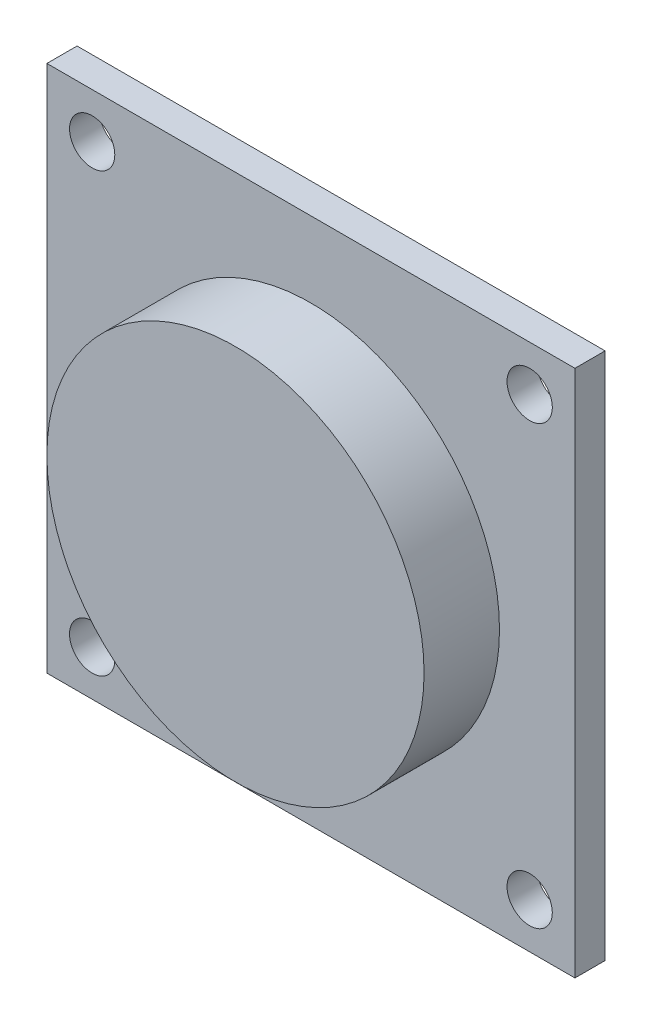
SolidWorks part; units mm, degrees
ref_plane "Front Plane" through (0, 0, 0) normal (0, 0, 1) x (1, 0, 0)
ref_plane "Top Plane" through (0, 0, 0) normal (0, 1, 0) x (1, 0, 0)
ref_plane "Right Plane" through (0, 0, 0) normal (1, 0, 0) x (0, 0, -1)
sketch "Sketch1" plane through (0, 0, 0) normal (0, 0, 1) x (1, 0, 0)
  line L1 (35, 35) -> (-35, 35)
  line L2 (35, 35) -> (35, -35)
  line L3 (35, -35) -> (-35, -35)
  line L4 (-35, 35) -> (-35, -35)
  line L5 (35, 35) -> (-35, -35) construction
  line L6 (35, -35) -> (-35, 35) construction
  point P0 (0, 0)
  dimension "D1" = 70
  dimension "D2" = 70
extrude "Boss-Extrude1" add sketch "Sketch1" along normal blind 4
sketch "Sketch2" plane through (0, 0, 4) normal (0, 0, 1) x (1, 0, 0)
  circle A0 centre (0, 0) radius 25
  dimension "D1" = 50
extrude "Boss-Extrude2" add sketch "Sketch2" along normal blind 10
sketch "Sketch3" plane through (0, 0, 0) normal (0, 0, -1) x (-1, 0, 0)
  circle A0 centre (0, 0) radius 25
  dimension "D1" = 50
extrude "Cut-Extrude1" cut sketch "Sketch3" against normal blind 4
fillet "Fillet1" radius 4 1 edges at (-25, 0, 0)
sketch "Sketch4" plane through (0, 0, 4) normal (0, 0, 1) x (1, 0, 0)
  line L0 (-39.3388, 0) -> (37.8701, 0) construction
  line L1 (0, 42.9055) -> (0, -44.8987) construction
  line L2 (35, 35) -> (-35, 35) construction
  line L3 (-35, 35) -> (-35, -35) construction
  circle A0 centre (-29, 29) radius 3.0003
  circle A1 centre (29, 29) radius 3.0003
  circle A2 centre (-29, -29) radius 3.0003
  circle A3 centre (29, -29) radius 3.0003
  dimension "D1" = 6.0006
  dimension "D2" = 6
  dimension "D3" = 6
extrude "Cut-Extrude2" cut sketch "Sketch4" against normal up to next (4 mm away)
sketch "Sketch5" plane through (0, 0, 4) normal (0, 0, -1) x (-1, 0, 0)
sketch "Sketch6" plane through (0, 0, 14) normal (0, 0, 1) x (1, 0, 0)
  arc A0 (-18.9537, 0) -> (18.9537, 0) centre (0, 0) cw
  point P4 (0, 0)
  point P5 (0, 0)
